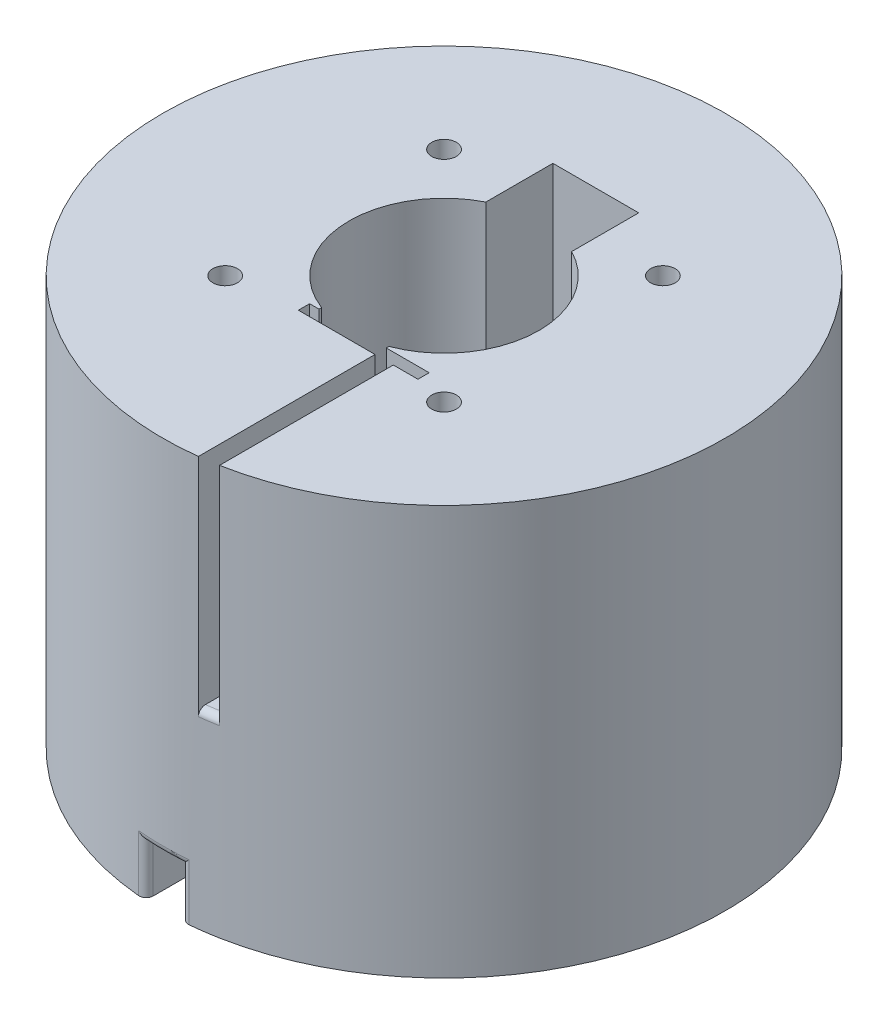
SolidWorks part; units mm, degrees
note: '?' marks a value the reader was unsure of.
material "ABS"
ref_plane "Front Plane" through (0, 0, 0) normal (0, 0, 1) x (1, 0, 0)
ref_plane "Top Plane" through (0, 0, 0) normal (0, 1, 0) x (1, 0, 0)
ref_plane "Right Plane" through (0, 0, 0) normal (1, 0, 0) x (0, 0, -1)
ref_plane "Plane1" through (0, 0, -5.455) normal (0, 0, 1) x (1, 0, 0)
ref_axis "Axis1" through (0, 63.175, -5.455) along (0, -1, 0)?
sketch "Sketch1" plane through (0, 0, 0) normal (0, 1, 0) x (1, 0, 0)
  line L1 (-6.1, -5.895) -> (6.1, -5.895)
  line L2 (-6.1, -5.895) -> (-6.1, 16.805)
  line L3 (-6.1, 16.805) -> (6.1, 16.805)
  line L4 (6.1, -5.895) -> (6.1, 16.805)
  line L5 (-6.1, -5.895) -> (6.1, 16.805) construction
  line L6 (-6.1, 16.805) -> (6.1, -5.895) construction
  circle A0 centre (0, 0) radius 40
  dimension "75" = 80
  dimension "D2" = 12.2
  dimension "D3" = 22.7
extrude "Boss-Extrude1" add sketch "Sketch1" along normal blind 16.35
sketch "Sketch3" plane through (0, 0, 0) normal (0, -1, 0) x (1, 0, 0)
  line L0 (-6.1, 5.895) -> (6.1, 5.895) construction
  line L1 (-2.5, 5.895) -> (2.5, 5.895)
  line L2 (-2.5, 5.895) -> (-2.5, 40)
  line L3 (-2.5, 40) -> (2.5, 40)
  line L4 (2.5, 5.895) -> (2.5, 40)
  line L5 (-2.5, 5.895) -> (2.5, 40) construction
  line L6 (-2.5, 40) -> (2.5, 5.895) construction
  circle A0 centre (0, 0) radius 40 construction
  point P4 (0, 22.9475)
  point P8 (0, 5.895)
  dimension "D1" = 5
extrude "Cut-Extrude1" cut sketch "Sketch3" against normal blind 7
sketch "Sketch4" plane through (0, 0, 0) normal (0, -1, 0) x (1, 0, 0)
  line L0 (0, 0) -> (-15.5563, 15.5563) construction
  line L1 (-1000, 0) -> (49000, 0) construction
  circle A0 centre (-15.5563, 15.5563) radius 1.75
  circle A1 centre (15.5563, 15.5563) radius 1.75
  circle A2 centre (15.5563, -15.5563) radius 1.75
  circle A3 centre (-15.5563, -15.5563) radius 1.75
  point P15 (0, 0)
  dimension "D1" = 3.5
  dimension "D2" = 22
  dimension "D3" = 45
  dimension "D5" = 31.1127
  dimension "D6" = 22
  dimension "D4" = 4
extrude "Cut-Extrude2" cut sketch "Sketch4" against normal blind 8
sketch "Sketch2" plane through (0, 16.35, 0) normal (0, 1, 0) x (1, 0, 0)
  line L0 (6.1, 16.805) -> (-6.1, 16.805) construction
  line L1 (-6.1, -10.67) -> (6.1, -10.67)
  line L2 (-6.1, -10.67) -> (-6.1, 21.58)
  line L3 (-6.1, 21.58) -> (6.1, 21.58)
  line L4 (6.1, -10.67) -> (6.1, 21.58)
  line L5 (-6.1, -10.67) -> (6.1, 21.58) construction
  line L6 (-6.1, 21.58) -> (6.1, -10.67) construction
  circle A0 centre (0, 0) radius 40
  circle A1 centre (0, 0) radius 40 construction
  point P0 (0, 0)
  dimension "D1" = 32.25
extrude "Boss-Extrude2" add sketch "Sketch2" along normal blind 8.3
sketch "Sketch5" plane through (0, 16.35, 0) normal (0, 1, 0) x (1, 0, 0)
  line L0 (6.1, 21.58) -> (-6.1, 21.58) construction
  line L1 (-1000, 5.455) -> (49000, 5.455) construction
  circle A0 centre (0, 19.58) radius 1
  circle A1 centre (0, -8.67) radius 1
  dimension "D2" = 2
  dimension "D1" = 2
extrude "Cut-Extrude3" cut sketch "Sketch5" against normal blind 8
sketch "Sketch6" plane through (0, 24.65, 0) normal (0, 1, 0) x (1, 0, 0)
  line L0 (6.1, 12.0433) -> (6.1, 21.58)
  line L1 (6.1, -10.67) -> (6.1, 21.58) construction
  line L2 (6.1, 21.58) -> (-6.1, 21.58)
  line L3 (-6.1, 21.58) -> (-6.1, 12.0433)
  line L4 (-6.1, 21.58) -> (-6.1, -10.67) construction
  arc A1 (-6.1, 12.0433) -> (6.1, 12.0433) centre (0, 0) ccw
  circle A2 centre (0, 0) radius 40
  circle A3 centre (0, 0) radius 40 construction
  dimension "D1" = 27
extrude "Boss-Extrude3" add sketch "Sketch6" along normal blind 2.5
sketch "Sketch7" plane through (0, 27.15, 0) normal (0, 1, 0) x (1, 0, 0)
  line L0 (-6.1, 12.0433) -> (-6.1, 21.58)
  line L1 (-6.11, -13) -> (-4.7901, -13)
  line L2 (-6.11, -13) -> (-6.11, -14.6)
  line L3 (-6.11, -14.6) -> (4.79, -14.6)
  line L4 (10.89, -13) -> (10.89, -14.6)
  line L5 (-6.1, 21.58) -> (-6.1, 12.0433) construction
  line L6 (6.1, 21.58) -> (-6.1, 21.58) construction
  line L7 (-6.1, 21.58) -> (6.1, 21.58)
  line L8 (6.1, 21.58) -> (6.1, 12.0433)
  line L9 (4.79, -13) -> (10.89, -13)
  line L10 (4.79, -14.6) -> (4.79, -39.7122)
  line L11 (7.39, -14.6) -> (7.39, -39.3114)
  line L12 (7.39, -14.6) -> (7.39, -39.7122) construction
  line L13 (7.39, -14.6) -> (10.89, -14.6)
  line L14 (4.79, -39.7122) -> (7.39, -39.7122)
  line L15 (7.39, -39.7122) -> (7.39, -39.3114)
  line L16 (4.79, -13) -> (4.79, -12.6216)
  line L17 (-4.7901, -13) -> (-4.7901, -12.6216)
  circle A0 centre (0, 0) radius 13 construction
  arc A1 (-6.1, 12.0433) -> (-4.7901, -12.6216) centre (0, 0) ccw
  circle A3 centre (0, 0) radius 40
  circle A4 centre (0, 0) radius 40 construction
  arc A5 (4.79, -12.6216) -> (6.1, 12.0433) centre (0, 0) ccw
  circle M15 centre (0, 0) radius 40
  line M16 (6.1, 21.58) -> (6.1, 12.0433)
  arc M17 (6.1, 12.0433) -> (-6.1, 12.0433) centre (0, 0) cw
  line M18 (-6.1, 12.0433) -> (-6.1, 21.58)
  line M19 (-6.1, 21.58) -> (6.1, 21.58)
  dimension "D1" = 26
  dimension "D4" = 6.11
  dimension "D2" = 1.6
  dimension "D3" = 17
  dimension "D5" = 10.9
  dimension "D7" = 0.3784
  dimension "D6" = 2.6
extrude "Boss-Extrude4" add sketch "Sketch7" along normal blind 31.05 contours L13 L11 L10 L3 L2 L1 L9 L4 M15 M17 M18 M19 M16
sketch "Sketch8" plane through (0, 58.2, 0) normal (0, 1, 0) x (1, 0, 0)
  line L0 (-15.5563, 15.5563) -> (0, 0) construction
  line L1 (-1000, 0) -> (49000, 0) construction
  circle A0 centre (-15.5563, 15.5563) radius 1.75
  circle A1 centre (15.5563, 15.5563) radius 1.75
  circle A2 centre (15.5563, -15.5563) radius 1.75
  circle A3 centre (-15.5563, -15.5563) radius 1.75
  point P15 (0, 0)
  dimension "D1" = 3.5
  dimension "D2" = 22
  dimension "D3" = 45
  dimension "D5" = 22
  dimension "D6" = 31.1127
  dimension "D4" = 4
extrude "Cut-Extrude4" cut sketch "Sketch8" against normal blind 8
fillet "Fillet1" radius 1 4 edges at (-2.5, 3.5, 39.9218) (2.5, 3.5, 39.9218) (0, 7, 40) (6.0933, 27.15, 39.5332)
